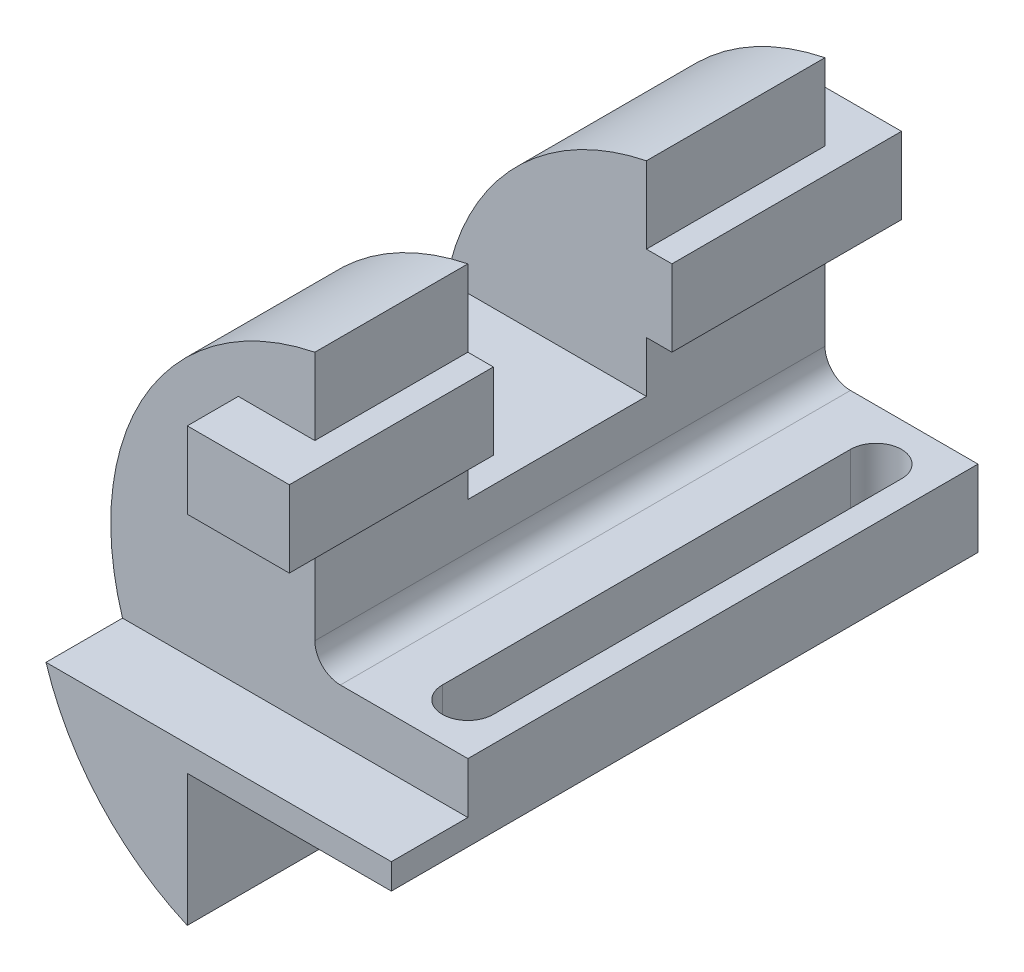
SolidWorks part; units mm, degrees
material "1060 Alloy"
ref_plane "Front Plane" through (0, 0, 0) normal (0, 0, 1) x (1, 0, 0)
ref_plane "Top Plane" through (0, 0, 0) normal (0, 1, 0) x (1, 0, 0)
ref_plane "Right Plane" through (0, 0, 0) normal (1, 0, 0) x (0, 0, -1)
sketch "Sketch1" plane through (0, 0, 0) normal (0, 0, 1) x (1, 0, 0)
  line L0 (0, -106.967) -> (0, 106.967) construction
  line L1 (0, 50) -> (0, -5)
  line L2 (0, -5) -> (20, -5)
  line L3 (20, -5) -> (20, -20)
  line L4 (20, -20) -> (0, -20)
  line L5 (0, -20) -> (0, -50)
  arc A0 (0, 50) -> (0, -50) centre (0, 0) ccw
  point P3 (0, 0)
  point P4 (0, 0)
  dimension "D1" = 100
  dimension "D2" = 15
  dimension "D3" = 55
  dimension "D4" = 20
extrude "Boss-Extrude1" add sketch "Sketch1" against normal blind 115
sketch "Sketch2" plane through (0, 0, 0) normal (0, 0, 1) x (1, 0, 0)
  line L0 (0, -5) -> (-5, -5)
  line L1 (-10, 0) -> (-10, 48.9898)
  line L2 (0, -5) -> (0, 50) construction
  line L3 (0, 50) -> (0, -5)
  arc A0 (0, 50) -> (-10, 48.9898) centre (0, 0) ccw
  arc A1 (0, 50) -> (0, -50) centre (0, 0) ccw construction
  circle A2 centre (-5, 0) radius 5 construction
  arc A3 (-10, 0) -> (-5, -5) centre (-5, 0) ccw
  dimension "D2" = 10
  dimension "D1" = 10
extrude "Cut-Extrude4" cut sketch "Sketch2" against normal blind 115
sketch "Sketch6" plane through (0, 0, 0) normal (0, 0, 1) x (1, 0, 0)
  line L0 (0, -20) -> (-20, -20)
  line L1 (0, -50) -> (0, -20) construction
  line L2 (-20, -20) -> (-20, -45.8258)
  line L3 (0, -20) -> (0, -50)
  arc A0 (-10, 48.9898) -> (0, -50) centre (0, 0) ccw construction
  arc A1 (0, -50) -> (-20, -45.8258) centre (0, 0) cw
  point P12 (-10, -20)
  dimension "D1" = 40
extrude "Cut-Extrude5" cut sketch "Sketch6" against normal blind 115
sketch "Sketch7" plane through (0, 0, 0) normal (0, 0, 1) x (1, 0, 0)
  line L2 (20, -5) -> (-5, -5)
  line L3 (20, -5) -> (-5, -5) construction
  line L4 (-10, 0) -> (-10, 48.9898)
  line L5 (20, -5) -> (20, -15)
  line L6 (20, -20) -> (20, -5) construction
  line L7 (20, -15) -> (-47.697, -15)
  arc A1 (-10, 0) -> (-5, -5) centre (-5, 0) ccw construction
  arc A2 (-10, 0) -> (-5, -5) centre (-5, 0) ccw
  arc A3 (-10, 48.9898) -> (-47.697, -15) centre (0, 0) ccw
  dimension "D1" = 10
extrude "Cut-Extrude7" cut sketch "Sketch7" against normal blind 15
sketch "Sketch8" plane through (-10, 0, 0) normal (1, 0, 0) x (0, 0, -1)
  line L0 (115, 48.9898) -> (15, 48.9898) construction
  line L1 (45, 48.9898) -> (80, 48.9898)
  line L2 (45, 48.9898) -> (45, 8.9898)
  line L3 (45, 8.9898) -> (80, 8.9898)
  line L4 (80, 48.9898) -> (80, 8.9898)
  line L5 (15, 0) -> (15, 48.9898) construction
  dimension "D1" = 40
  dimension "D2" = 30
  dimension "D3" = 35
extrude "Cut-Extrude8" cut sketch "Sketch8" against normal blind 55
sketch "Sketch9" plane through (0, 0, -15) normal (0, 0, 1) x (1, 0, 0)
  line L0 (-10, 8.9898) -> (-49.1852, 8.9898) construction
  line L1 (-10, 0) -> (-10, 48.9898) construction
  line L3 (-25, 33.9898) -> (-5, 33.9898)
  line L4 (-25, 33.9898) -> (-25, 18.9898)
  line L5 (-25, 18.9898) -> (-5, 18.9898)
  line L6 (-5, 33.9898) -> (-5, 18.9898)
  arc A0 (-10, 48.9898) -> (-47.697, -15) centre (0, 0) ccw construction
  dimension "D1" = 40
  dimension "D2" = 5
  dimension "D3" = 20
  dimension "D4" = 15
  dimension "D5" = 15
extrude "Boss-Extrude2" add sketch "Sketch9" against normal blind 30 and the other way blind 10
sketch "Sketch10" plane through (0, 0, -115) normal (0, 0, -1) x (-1, 0, 0)
  line L0 (10, 8.9898) -> (49.1852, 8.9898)
  line L1 (10, 48.9898) -> (10, 0) construction
  line L3 (5, 33.9898) -> (25, 33.9898)
  line L4 (5, 33.9898) -> (5, 18.9898)
  line L5 (5, 18.9898) -> (25, 18.9898)
  line L6 (25, 33.9898) -> (25, 18.9898)
  arc A0 (20, -45.8258) -> (10, 48.9898) centre (0, 0) ccw construction
  line M8 (10, 48.9898) -> (10, 0)
  dimension "D1" = 40
  dimension "D2" = 15
  dimension "D3" = 10
  dimension "D4" = 15
extrude "Boss-Extrude4" add sketch "Sketch10" against normal blind 35 and the other way blind 10 contours L6 L3 L5 M8 | L4 L5 L3 M8 region at (-7.5, 26.4898, -115) region at (-17.5, 26.4898, -115)
sketch "Sketch11" plane through (0, -5, 0) normal (0, 1, 0) x (1, 0, 0)
  line L0 (-47.697, 15) -> (20, 15) construction
  line L1 (20, 115) -> (-5, 115) construction
  line L2 (20, 115) -> (20, 15) construction
  line L3 (5, 105) -> (5, 25)
  line L4 (15, 105) -> (15, 25)
  arc A0 (5, 25) -> (15, 25) centre (10, 25) ccw
  arc A1 (15, 105) -> (5, 105) centre (10, 105) ccw
  dimension "D1" = 10
  dimension "D2" = 10
  dimension "D3" = 10
  dimension "D4" = 10
  dimension "D5" = 10
  dimension "D6" = 10
extrude "Cut-Extrude9" cut sketch "Sketch11" against normal blind 35
